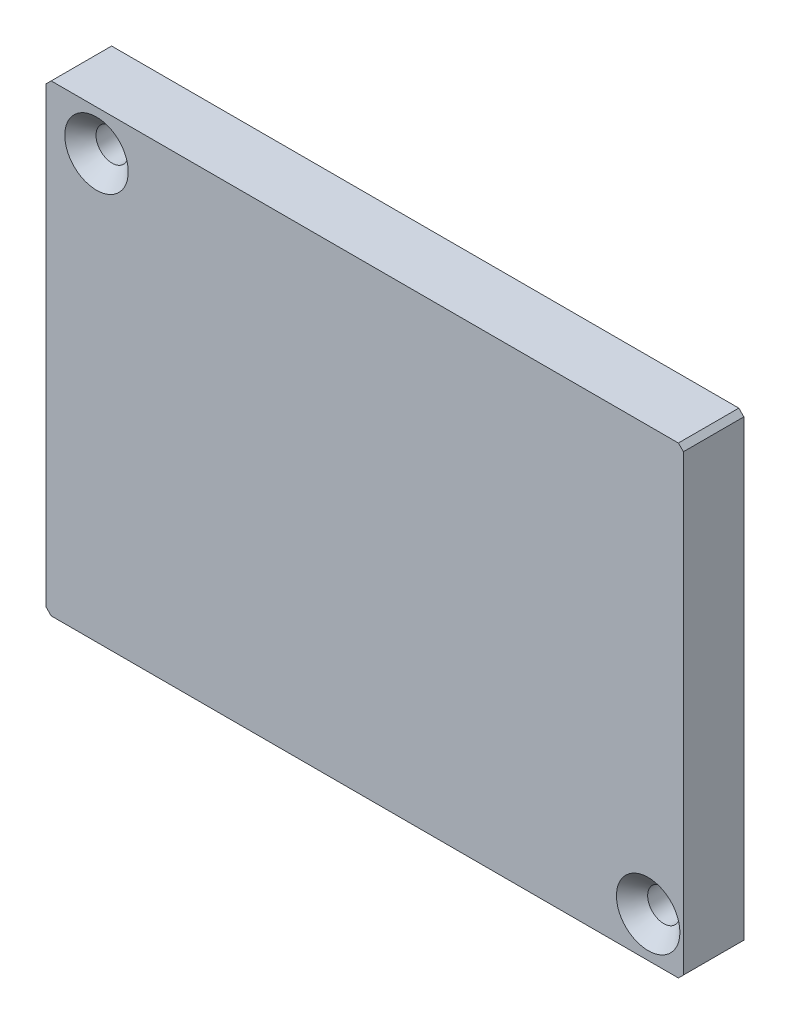
SolidWorks part; units mm, degrees
ref_plane "Přední rovina" through (0, 0, 0) normal (0, 0, 1) x (1, 0, 0)
ref_plane "Horní rovina" through (0, 0, 0) normal (0, 1, 0) x (1, 0, 0)
ref_plane "Pravá rovina" through (0, 0, 0) normal (1, 0, 0) x (0, 0, -1)
sketch "Skica1" plane through (0, 0, 0) normal (0, 0, 1) x (1, 0, 0)
  line L20 (-326.8797, 22.5) -> (-326.8797, -22.5)
  line L21 (-326.8797, -22.5) -> (-326.3797, -23)
  line L22 (-326.3797, -23) -> (-264.1099, -23)
  line L23 (-264.1099, -23) -> (-263.6099, -22.5)
  line L24 (-263.6099, -22.5) -> (-263.6099, 22.5)
  line L25 (-263.6099, 22.5) -> (-264.1099, 23)
  line L26 (-264.1099, 23) -> (-326.3797, 23)
  line L27 (-326.3797, 23) -> (-326.8797, 22.5)
  line L28 (-326.8797, 22.5) -> (-326.8797, -22.5)
  line L29 (-326.8797, -22.5) -> (-326.3797, -23)
  line L30 (-326.3797, -23) -> (-264.1099, -23)
  line L31 (-264.1099, -23) -> (-263.6099, -22.5)
  line L32 (-263.6099, -22.5) -> (-263.6099, 22.5)
  line L33 (-263.6099, 22.5) -> (-264.1099, 23)
  line L34 (-264.1099, 23) -> (-326.3797, 23)
  line L35 (-326.3797, 23) -> (-326.8797, 22.5)
  circle A0 centre (-276.6099, 8.8875) radius 2.25 construction
  circle A1 centre (-298.6099, -13.1125) radius 2.25 construction
  circle A6 centre (-276.6099, 8.8875) radius 2.25 construction
  circle A7 centre (-298.6099, -13.1125) radius 2.25 construction
  circle A8 centre (-298.6099, -13.1125) radius 3.25 construction
  circle A9 centre (-276.6099, 8.8875) radius 3.25 construction
  circle A10 centre (-267.1099, 19) radius 3.1 construction
  circle A11 centre (-267.1099, 19) radius 3.1 construction
  circle A12 centre (-321.8797, -19) radius 3.1 construction
  circle A13 centre (-321.8797, -19) radius 3.1 construction
  dimension "D1" = 0
  dimension "D2" = 1
extrude "Přidat vysunutím2" add sketch "Skica1" along normal blind 6
hole_wizard "Ø6.3 (6.3) průměr díry1" positions "3DSkica1" profile "Skica2" hole size "Ø6.3" standard "ISO"
sketch3d "3DSkica1"
  point P0 (-267.1099, 19, 0)
  point P3 (-276.6099, 8.8875, 0)
  point P6 (-298.6099, -13.1125, 0)
  point P9 (-321.8797, -19, 0)
  point P13 (-267.1099, 19, 0)
  point P15 (-276.6099, 8.8875, 0)
  point P17 (-298.6099, -13.1125, 0)
  point P21 (-298.6099, -13.1125, 0)
  point P23 (-276.6099, 8.8875, 0)
  point P25 (-267.1099, 19, 0)
  point P27 (-321.8797, -19, 0)
  point P29 (0, 0, 0)
  point P30 (0, 0, 0)
  point P31 (0, 0, 0)
  point P32 (0, 0, 0)
sketch "Skica2" plane through (-321.8797, -19, 0) normal (1, 0, 0) x (0, 1, 0)
  line L0 (0, 0) -> (0, 4.8927)
  line L1 (0, 4.8927) -> (3.15, 3)
  line L2 (3.15, 3) -> (3.15, 0.05)
  line L3 (3.15, 0.05) -> (3.2, 0)
  line L5 (3.2, 0) -> (0, 0)
  line L6 (-3.15, 0.05) -> (-3.2, 0) construction
  line L10 (0, 4.8927) -> (-3.15, 3) construction
  line L11 (0, -6.35) -> (0, 107.95) construction
  dimension "Průměr díry" = 6.3
  dimension "Hloubka díry" = 3
  dimension "Průměr blíz. kuž. zahloubení" = 6.4
  dimension "Úhel blíz. kuž. zahloubení" = 90
  dimension "Úhel vrtání" = 118
hole_wizard "Kuželové zahloubení pro M3 šroubu se zápustnou hlavou plochou1" positions "3DSkica2" profile "Skica3" countersink size "M3" standard "ISO" end condition up to next
sketch3d "3DSkica2"
  point P0 (-321.8797, 19, 6)
  point P2 (-267.1099, -19, 6)
  point P6 (0, 0, 0)
  point P8 (0, 0, 0)
sketch "Skica3" plane through (-321.8797, 19, 6) normal (1, 0, 0) x (0, -1, 0)
  line L0 (0, 0) -> (0, 6)
  line L1 (0, 6) -> (1.6, 6)
  line L2 (1.6, 6) -> (1.6, 1.55)
  line L3 (1.6, 1.55) -> (3.15, 0)
  line L5 (3.15, 0) -> (0, 0)
  line L6 (-1.6, 1.55) -> (-3.15, 0) construction
  line L11 (0, -6.35) -> (0, 107.95) construction
  dimension "Průměr díry skrz" = 3.2
  dimension "Hloubka díry skrz" = 6
  dimension "Průměr blíz. kuž. zahloubení" = 6.3
  dimension "Úhel blíz. kuž. zahloubení" = 90
